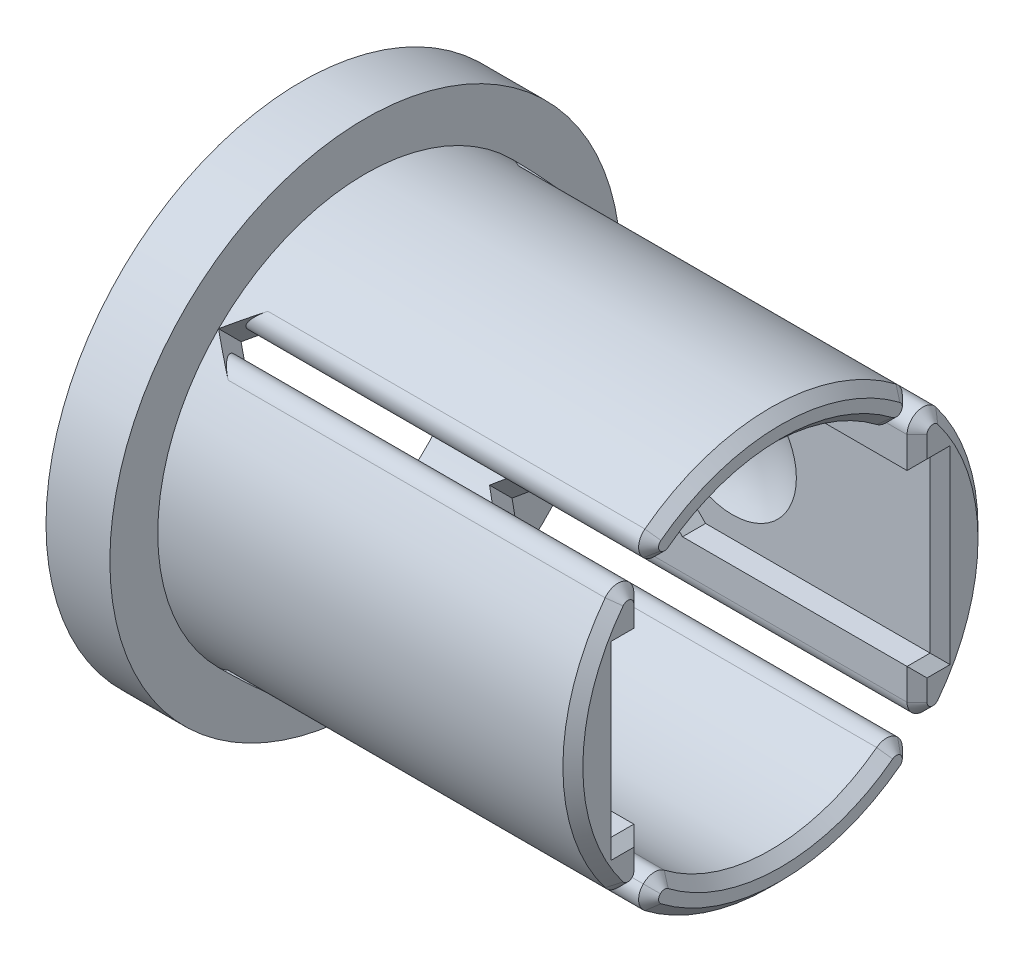
SolidWorks part; units mm, degrees
ref_plane "Front Plane" through (0, 0, 0) normal (0, 0, 1) x (1, 0, 0)
ref_plane "Top Plane" through (0, 0, 0) normal (0, 1, 0) x (1, 0, 0)
ref_plane "Right Plane" through (0, 0, 0) normal (1, 0, 0) x (0, 0, -1)
sketch "Sketch1" plane through (0, 0, 0) normal (0, 0, 1) x (1, 0, 0)
  line L0 (0, 13.97) -> (38.1, 13.97)
  line L1 (38.1, 13.97) -> (38.1, 16.51)
  line L2 (38.1, 16.51) -> (5.08, 16.51)
  line L3 (5.08, 16.51) -> (5.08, 20.32)
  line L4 (5.08, 20.32) -> (0, 20.32)
  line L6 (0, 0) -> (66.9506, 0) construction
  line L7 (0, 13.97) -> (0, 20.32)
  line L8 (0, 0) -> (0, 36.5805) construction
  dimension "D1" = 13.97
  dimension "D2" = 16.51
  dimension "D3" = 20.32
  dimension "D4" = 5.08
  dimension "D5" = 38.1
revolve "Revolve1" add sketch "Sketch1" angle 360 about L6
sketch "Sketch3" plane through (38.1, 0, 0) normal (1, 0, 0) x (0, 0, -1)
  line L0 (0, 0) -> (36.586, 0) construction
  line L1 (0, 0) -> (25.7533, 25.7533) construction
  line L2 (10.4236, 9.3011) -> (12.2221, 11.0996)
  line L3 (9.3011, 10.4236) -> (11.0996, 12.2221)
  line L4 (10.4236, -9.3011) -> (12.2221, -11.0996)
  line L5 (9.3011, -10.4236) -> (11.0996, -12.2221)
  line L6 (-9.3011, -10.4236) -> (-11.0996, -12.2221)
  line L7 (-10.4236, -9.3011) -> (-12.2221, -11.0996)
  line L8 (-10.4236, 9.3011) -> (-12.2221, 11.0996)
  line L9 (-9.3011, 10.4236) -> (-11.0996, 12.2221)
  circle A0 centre (0, 0) radius 13.97 construction
  circle A1 centre (0, 0) radius 16.51 construction
  arc A2 (10.4236, 9.3011) -> (9.3011, 10.4236) centre (0, 0) ccw
  arc A3 (12.2221, 11.0996) -> (11.0996, 12.2221) centre (0, 0) ccw
  arc A4 (11.0996, -12.2221) -> (12.2221, -11.0996) centre (0, 0) ccw
  arc A5 (9.3011, -10.4236) -> (10.4236, -9.3011) centre (0, 0) ccw
  arc A6 (-12.2221, -11.0996) -> (-11.0996, -12.2221) centre (0, 0) ccw
  arc A7 (-10.4236, -9.3011) -> (-9.3011, -10.4236) centre (0, 0) ccw
  arc A8 (-11.0996, 12.2221) -> (-12.2221, 11.0996) centre (0, 0) ccw
  arc A9 (-9.3011, 10.4236) -> (-10.4236, 9.3011) centre (0, 0) ccw
  point P27 (0, 0)
  dimension "D1" = 45
  dimension "D2" = 0.7937
  dimension "D3" = 0.7937
  dimension "D4" = 4
extrude "Cut-Extrude1" cut sketch "Sketch3" against normal up to surface (33.02 mm away) up to face at (5.08, 0, 20.32)
chamfer "Chamfer3" distance 0.7937 angle 45 8 edges at (5.08, -11.3228, -10.2003) (5.08, -10.2003, -11.3228) (5.08, -11.3228, 10.2003) (5.08, -10.2003, 11.3228) (5.08, 10.2003, -11.3228) (5.08, 11.3228, -10.2003) (5.08, 10.2003, 11.3228) (5.08, 11.3228, 10.2003)
fillet "Fillet1" radius 1.27 16 edges at (21.9869, -12.2221, -11.0996) (21.9869, -10.4236, -9.3011) (21.9869, -11.0996, -12.2221) (21.9869, -9.3011, -10.4236) (21.9869, -12.2221, 11.0996) (21.9869, -10.4236, 9.3011) (21.9869, -9.3011, 10.4236) (21.9869, -11.0996, 12.2221) (21.9869, 9.3011, -10.4236) (21.9869, 11.0996, -12.2221) (21.9869, 12.2221, -11.0996) (21.9869, 10.4236, -9.3011) (21.9869, 10.4236, 9.3011) (21.9869, 12.2221, 11.0996) (21.9869, 9.3011, 10.4236) (21.9869, 11.0996, 12.2221)
sketch "Sketch4" plane through (38.1, 0, 0) normal (1, 0, 0) x (0, 0, -1)
  line L0 (0, 0) -> (-20.0952, 0) construction
  line L1 (0, -14.8989) -> (0, 15.5414) construction
  line L2 (-12.1363, 9.2178) -> (0, 9.2178) construction
  line L3 (-12.1363, -9.2178) -> (0, -9.2178) construction
  line L4 (-10.8663, 9.2178) -> (-10.8663, -9.2178)
  line L5 (10.8663, 9.2178) -> (10.8663, -9.2178)
  arc A0 (13.1477, 9.9859) -> (13.1477, -9.9859) centre (0, 0) cw
  arc A1 (11.2383, 10.1158) -> (13.1477, 9.9859) centre (12.1363, 9.2178) cw
  arc A2 (10.8663, 9.2178) -> (11.2383, 10.1158) centre (12.1363, 9.2178) cw
  arc A3 (11.2383, -10.1158) -> (10.8663, -9.2178) centre (12.1363, -9.2178) cw
  arc A4 (13.1477, -9.9859) -> (11.2383, -10.1158) centre (12.1363, -9.2178) cw
  arc A6 (-13.1477, -9.9859) -> (-11.2383, -10.1158) centre (-12.1363, -9.2178) ccw
  arc A7 (-11.2383, -10.1158) -> (-11.125, -8.4496) centre (-12.1363, -9.2178) ccw
  arc A8 (-11.125, 8.4496) -> (-11.125, -8.4496) centre (0, 0) ccw
  arc A9 (-11.125, 8.4496) -> (-11.2383, 10.1158) centre (-12.1363, 9.2178) ccw
  arc A10 (-11.2383, 10.1158) -> (-13.1477, 9.9859) centre (-12.1363, 9.2178) ccw
  arc A11 (-13.1477, 9.9859) -> (-13.1477, -9.9859) centre (0, 0) ccw
  arc A12 (-13.1477, -9.9859) -> (-11.2383, -10.1158) centre (-12.1363, -9.2178) ccw
  arc A13 (-11.2383, -10.1158) -> (-10.8663, -9.2178) centre (-12.1363, -9.2178) ccw
  arc A15 (-10.8663, 9.2178) -> (-11.2383, 10.1158) centre (-12.1363, 9.2178) ccw
  arc A16 (-11.2383, 10.1158) -> (-13.1477, 9.9859) centre (-12.1363, 9.2178) ccw
  arc A17 (-13.1477, 9.9859) -> (-13.1477, -9.9859) centre (0, 0) ccw
  dimension "D1" = 0
extrude "Boss-Extrude2" add sketch "Sketch4" against normal blind 31.75
sketch "Sketch6" plane through (0, 0, -10.8663) normal (0, 0, 1) x (1, 0, 0)
  line L6 (12.7, 0) -> (53.3168, 0) construction
  line L7 (38.1, 9.2178) -> (38.1, -9.2178) construction
  line L8 (38.1, 6.7469) -> (38.1, -6.7469)
  line L9 (38.1, 6.7469) -> (19.4469, 6.7469)
  line L10 (19.4469, 6.7469) -> (14.4961, 1.7961)
  line L11 (14.4961, -1.7961) -> (19.4469, -6.7469)
  line L12 (19.4469, -6.7469) -> (38.1, -6.7469)
  arc A0 (14.4961, 1.7961) -> (14.4961, -1.7961) centre (16.2921, 0) ccw
  dimension "D5" = 2.54
  dimension "D1" = 25.4
  dimension "D2" = 13.4937
  dimension "D3" = 45
extrude "Cut-Extrude2" cut sketch "Sketch6" against normal blind 1.8337
ref_plane "Plane1" through (21.59, 0, 0) normal (1, 0, 0) x (0, 0, -1)
sketch "Sketch9" plane through (21.59, 0, 0) normal (1, 0, 0) x (0, 0, -1)
  line L0 (0, 0) -> (17.5786, 0) construction
  line L1 (12.7, 0) -> (12.7, 5.08)
  line L3 (12.7, 0) -> (14.2875, 0)
  line L4 (12.7, -6.7469) -> (12.7, 6.7469) construction
  arc A0 (12.7, 5.08) -> (14.2875, 0) centre (5.3657, 0) cw
  dimension "D3" = 8.9217
  dimension "D1" = 5.08
  dimension "D2" = 1.5875
revolve "Cut-Revolve1" cut sketch "Sketch9" angle 360 about L0
ref_plane "Plane2" through (0, 0, 0) normal (0, 0, 1) x (1, 0, 0)
mirror "Mirror1" about plane through (0, 0, 0) normal (0, 0, 1) of "Cut-Extrude2", "Cut-Revolve1"
chamfer "Chamfer4" distance 3.302 angle 45 2 edges at (6.35, 0, -10.8663) (6.35, 0, 10.8663)
chamfer "Chamfer5" distance 0.7937 angle 45 28 edges at (38.1, -16.51, 0) (38.1, -13.97, 0) (38.1, -10.8693, 9.3039) (38.1, -12.2225, 10.4848) (38.1, -10.8693, -9.3039) (38.1, -12.2225, -10.4848) (38.1, 13.97, 0) (38.1, 0, -16.51) (38.1, 10.4214, -11.7311) (38.1, -10.4214, -11.7311) (38.1, 0, 16.51) (38.1, 10.4214, 11.7311) (38.1, -10.4214, 11.7311) (38.1, 16.51, 0) (38.1, 12.2225, 10.4848) (38.1, 10.8693, 9.3039) (38.1, 10.8693, -9.3039) (38.1, 12.2225, -10.4848) (38.1, -7.9823, 10.8663) (38.1, 7.9823, -10.8663) (38.1, -7.9823, -10.8663) (38.1, 0, -12.7) (38.1, 6.7469, -11.7832) (38.1, -6.7469, -11.7832) (38.1, 7.9823, 10.8663) (38.1, -6.7469, 11.7832) (38.1, 6.7469, 11.7832) (38.1, 0, 12.7)
